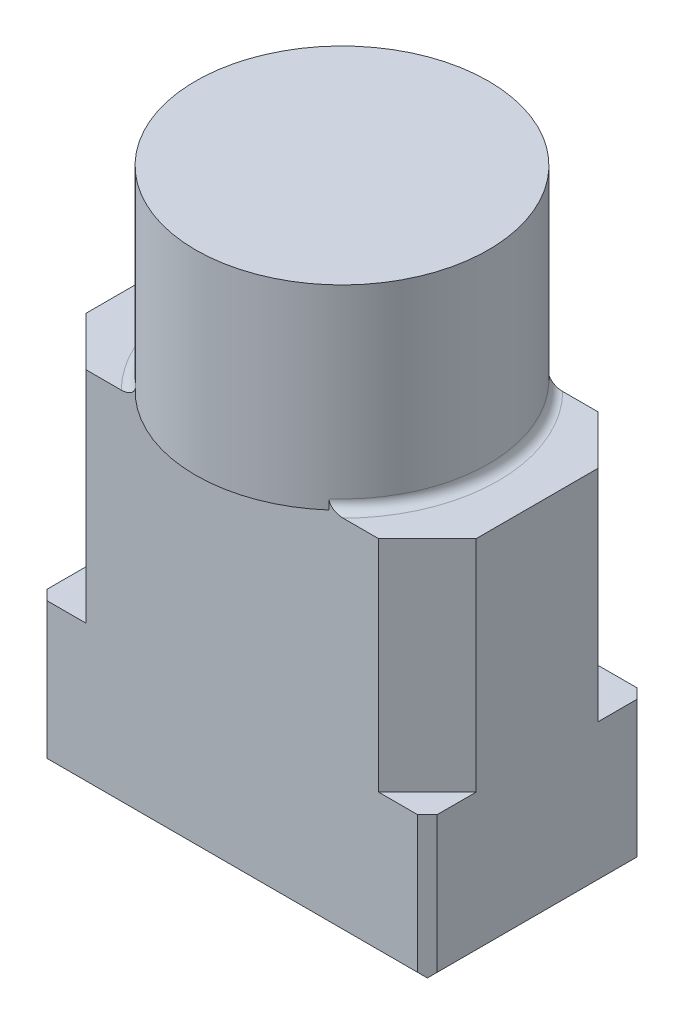
SolidWorks part; units mm, degrees
ref_plane "Front Plane" through (0, 0, 0) normal (0, 0, 1) x (1, 0, 0)
ref_plane "Top Plane" through (0, 0, 0) normal (0, 1, 0) x (1, 0, 0)
ref_plane "Right Plane" through (0, 0, 0) normal (1, 0, 0) x (0, 0, -1)
sketch "Sketch1" plane through (0, 0, 0) normal (0, 1, 0) x (1, 0, 0)
  circle A0 centre (0, 0) radius 30
extrude "Boss-Extrude1" add sketch "Sketch1" along normal blind 40
sketch "Sketch2" plane through (0, 0, 0) normal (0, -1, 0) x (1, 0, 0)
  line L1 (40, 22.5) -> (-40, 22.5)
  line L2 (40, 22.5) -> (40, -22.5)
  line L3 (40, -22.5) -> (-40, -22.5)
  line L4 (-40, 22.5) -> (-40, -22.5)
  line L5 (40, 22.5) -> (-40, -22.5) construction
  line L6 (40, -22.5) -> (-40, 22.5) construction
  point P0 (0, 0)
  dimension "D1" = 80
  dimension "D2" = 45
extrude "Boss-Extrude2" add sketch "Sketch2" along normal blind 45
chamfer "Chamfer1" distance 10 angle 45 4 edges at (-40, -22.5, 22.5) (40, -22.5, 22.5) (-40, -22.5, -22.5) (40, -22.5, -22.5)
ref_point "Point1"
sketch "Sketch4" plane through (0, -45, 0) normal (0, -1, 0) x (-1, 0, 0)
  line L0 (30, 22.5) -> (-30, 22.5) construction
  line L1 (-40, -22.5) -> (40, -22.5)
  line L2 (-40, -22.5) -> (-40, 22.5)
  line L3 (-40, 22.5) -> (40, 22.5)
  line L4 (40, -22.5) -> (40, 22.5)
  line L5 (-40, -22.5) -> (40, 22.5) construction
  line L6 (-40, 22.5) -> (40, -22.5) construction
  point P0 (0, 0)
  dimension "D1" = 80
extrude "Boss-Extrude3" add sketch "Sketch4" along normal blind 2
sketch "Sketch5" plane through (0, -47, 0) normal (0, -1, 0) x (1, 0, 0)
  line L1 (40, 22.5) -> (-40, 22.5)
  line L2 (40, 22.5) -> (40, -22.5)
  line L3 (40, -22.5) -> (-40, -22.5)
  line L4 (-40, 22.5) -> (-40, -22.5)
  line L5 (40, 22.5) -> (-40, -22.5) construction
  line L6 (40, -22.5) -> (-40, 22.5) construction
  point P0 (0, 0)
extrude "Boss-Extrude4" add sketch "Sketch5" along normal blind 30
chamfer "Chamfer2" distance 2 angle 45 4 edges at (40, -61, -22.5) (40, -61, 22.5) (-40, -61, 22.5) (-40, -61, -22.5)
chamfer "Chamfer3" distance 4 angle 45 4 edges at (0, -77, 22.5) (-40, -77, 0) (40, -77, 0) (0, -77, -22.5)
fillet "Fillet1" radius 2 2 edges at (30, 0, 0) (-30, 0, 0)
